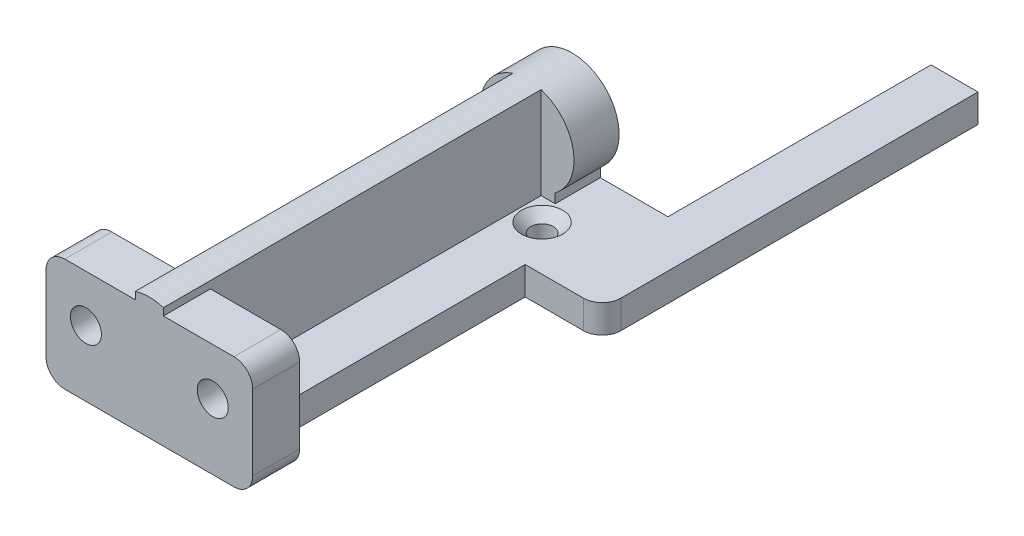
SolidWorks part; units mm, degrees
ref_plane "Front Plane" through (0, 0, 0) normal (0, 0, 1) x (1, 0, 0)
ref_plane "Top Plane" through (0, 0, 0) normal (0, 1, 0) x (1, 0, 0)
ref_plane "Right Plane" through (0, 0, 0) normal (1, 0, 0) x (0, 0, -1)
sketch "Sketch1" plane through (0, 0, 0) normal (0, 1, 0) x (1, 0, 0)
  line L0 (-4, -1.2) -> (0, -1.2) construction
  line L1 (7, -6) -> (-7, -6)
  line L2 (7, -6) -> (7, 6)
  line L3 (7, 6) -> (-7, 6)
  line L4 (-7, -6) -> (-7, 6)
  line L5 (7, -6) -> (-7, 6) construction
  line L6 (7, 6) -> (-7, -6) construction
  line L7 (0, 0) -> (0, -6) construction
  line L8 (0, 6) -> (0, 0) construction
  line L10 (7, -6) -> (10.2, -6)
  line L11 (7, -6) -> (7, 6)
  line L12 (7, 6) -> (10.2, 6)
  line L13 (10.2, -6) -> (10.2, 6)
  line L14 (0, -39) -> (0, -36.5) construction
  line L15 (10.2, -6) -> (15.2, -6)
  line L16 (10.2, -6) -> (10.2, 34)
  line L17 (10.2, 34) -> (15.2, 34)
  line L18 (15.2, -6) -> (15.2, 34)
  line L19 (-7, -6) -> (7, -6)
  line L20 (-7, -6) -> (-7, -39)
  line L21 (-7, -39) -> (7, -39)
  line L22 (7, -6) -> (7, -39)
  line L25 (-11, -34) -> (11, -34)
  line L26 (-11, -34) -> (-11, -39)
  line L27 (-11, -39) -> (11, -39)
  line L28 (11, -34) -> (11, -39)
  line L29 (-11, -34) -> (11, -39) construction
  line L30 (-11, -39) -> (11, -34) construction
  circle A0 centre (-4, -1.2) radius 1.15
  circle A1 centre (4, -1.2) radius 1.15
  point P0 (0, 0)
  dimension "D2" = 2.3
  dimension "D1" = 4
  dimension "D3" = 14
  dimension "D4" = 4.8
  dimension "D5" = 3.2
  dimension "D6" = 5
  dimension "D7" = 12
  dimension "D8" = 40
  dimension "D9" = 33
  dimension "D10" = 22
  dimension "D11" = 5
extrude "Boss-Extrude1" add sketch "Sketch1" along normal blind 3 contours L3 | L4 L1 L2 L3 A0 A1 | L11 L10 L13 L12 | L16 L15 L18 L17 | L20 L19 L22 L21 region at (0, 0, -0.0624)
sketch "Sketch3" plane through (0, 3, 0) normal (0, 1, 0) x (1, 0, 0)
  line L0 (0, 0) -> (0, 6) construction
  line L1 (-7, -39) -> (7, -39) construction
  line L5 (-5, 1.2) -> (-1.5, 1.2)
  line L6 (-5, 1.2) -> (-5, 6)
  line L7 (-5, 6) -> (5, 6)
  line L8 (5, 1.2) -> (5, 6)
  line L9 (-5, 1.2) -> (5, 6) construction
  line L10 (-5, 6) -> (5, 1.2) construction
  line L12 (10.2, 6) -> (-7, 6) construction
  line L13 (0, 0) -> (0, -39) construction
  line L15 (1.5, 1.2) -> (5, 1.2)
  line L17 (-1.5, 1.2) -> (-1.5, -39)
  line L18 (-1.5, -39) -> (1.5, -39)
  line L19 (1.5, 1.2) -> (1.5, -39)
  line L20 (-1.5, 1.2) -> (1.5, -39) construction
  line L21 (-1.5, -39) -> (1.5, 1.2) construction
  point P3 (0, -18.9)
  point P4 (0, 0)
  point P10 (0, 3.6)
  point P22 (0, -4.0862)
  point P23 (0, 0)
  dimension "D1" = 10
  dimension "D2" = 4.8
  dimension "D3" = 3
extrude "Boss-Extrude3" add sketch "Sketch3" along normal blind 10 contours L6 L7 L8 L15 L19 L18 L17 L5
hole_wizard "CSK for M2 Countersunk Flat Head Screw2" positions "3DSketch1" profile "Sketch5" countersink size "M2" standard "ISO" end condition through all
sketch3d "3DSketch1"
  line L0 (-4, 3, 1.2) -> (-4, 0, 1.2) construction
  line L1 (4, 3, 1.2) -> (4, 0, 1.2) construction
  point P0 (-4, 3, 1.2)
  point P4 (4, 3, 1.2)
sketch "Sketch5" plane through (-4, 3, 1.2) normal (1, 0, 0) x (0, 0, 1)
  line L0 (0, 0) -> (0, 3)
  line L1 (0, 3) -> (1.2, 3)
  line L2 (1.2, 3) -> (1.2, 1)
  line L3 (1.2, 1) -> (2.2, 0)
  line L5 (2.2, 0) -> (0, 0)
  line L6 (-1.2, 1) -> (-2.2, 0) construction
  line L11 (0, -6.35) -> (0, 107.95) construction
  dimension "Thru Hole Dia." = 2.4
  dimension "Thru Hole Depth" = 3
  dimension "Near C'Sink Dia." = 4.4
  dimension "Near C'Sink Angle" = 90
sketch "Sketch6" plane through (0, 0, -6) normal (0, 0, -1) x (-1, 0, 0)
  line L0 (0, 0) -> (0, 13) construction
  line L1 (5, 13) -> (-5, 13) construction
  line L2 (-5, 3) -> (5, 3) construction
  line L3 (-3, 3) -> (-3, 4)
  line L4 (3, 3) -> (3, 4)
  line L5 (-5, 13) -> (-5, 3) construction
  line L6 (5, 13) -> (5, 3) construction
  line L7 (-5, 13) -> (-5, 3)
  line L8 (5, 13) -> (5, 3)
  line L9 (5, 13) -> (-5, 13)
  line L10 (-5, 3) -> (-3, 3)
  line L11 (3, 3) -> (5, 3)
  arc A0 (3, 4) -> (-3, 4) centre (0, 8) ccw
  line M10 (5, 3) -> (5, 13)
  line M11 (5, 13) -> (-5, 13)
  line M12 (-5, 13) -> (-5, 3)
  dimension "D1" = 10
  dimension "D2" = 1
extrude "Cut-Extrude2" cut sketch "Sketch6" against normal through all contours A0 L9 M12 | A0 L8 M11 | A0 L4 L11 M10 | A0 L7 L10 L3 region at (4.2339, 4.2953, -6) region at (-4.2339, 4.2953, -6) region at (-3.8832, 11.8832, -6) region at (3.8832, 11.8832, -6)
extrude "Boss-Extrude4" add sketch "Sketch1<4>" along normal blind 12 contours L26 L27 L20 L25 | L28 L25 L22 L27 | L25 L20 L21 L22 region at (9, 0, 36.5) region at (0, 0, 36.5) region at (-9, 0, 36.5)
sketch "Sketch1<4>" plane through (0, 0, 0) normal (0, 1, 0) x (1, 0, 0) same geometry as "Sketch1"
sketch "Sketch7" plane through (0, 0, 34) normal (0, 0, -1) x (-1, 0, 0)
  line L0 (0, 0) -> (0, 12) construction
  line L2 (1.5, 12) -> (-1.5, 12) construction
  line L3 (6.75, 7) -> (0, 7) construction
  line L4 (5.1623, 9.75) -> (3.5746, 7)
  line L5 (3.5746, 7) -> (5.1623, 4.25)
  line L6 (5.1623, 4.25) -> (8.3377, 4.25)
  line L7 (8.3377, 4.25) -> (9.9254, 7)
  line L8 (9.9254, 7) -> (8.3377, 9.75)
  line L9 (8.3377, 9.75) -> (5.1623, 9.75)
  line L10 (1.5, 3) -> (7, 3) construction
  line L11 (-5.1623, 9.75) -> (-3.5746, 7)
  line L12 (-3.5746, 7) -> (-5.1623, 4.25)
  line L13 (-5.1623, 4.25) -> (-8.3377, 4.25)
  line L14 (-8.3377, 4.25) -> (-9.9254, 7)
  line L15 (-9.9254, 7) -> (-8.3377, 9.75)
  line L16 (-8.3377, 9.75) -> (-5.1623, 9.75)
  circle A0 centre (6.75, 7) radius 2.75 construction
  circle A1 centre (6.75, 7) radius 1.65
  circle A2 centre (-6.75, 7) radius 1.65
  point P20 (0, 0)
  point P28 (0, 0)
  dimension "D1" = 5.5
  dimension "D4" = 3.3
  dimension "D2" = 6.75
  dimension "D3" = 4
extrude "Cut-Extrude3" cut sketch "Sketch7" against normal through all contours A1 | A2
extrude "Cut-Extrude4" cut sketch "Sketch7<3>" against normal blind 2.5 contours L8 L9 L4 L5 L6 L7 | L11 L12 L13 L14 L15 L16
sketch "Sketch7<3>" plane through (0, 0, 34) normal (0, 0, -1) x (-1, 0, 0) same geometry as "Sketch7"
fillet "Fillet2" radius 2 5 edges at (15.2, 1.5, 6) (-11, 12, 36.5) (-11, 0, 36.5) (11, 0, 36.5) (11, 12, 36.5)
